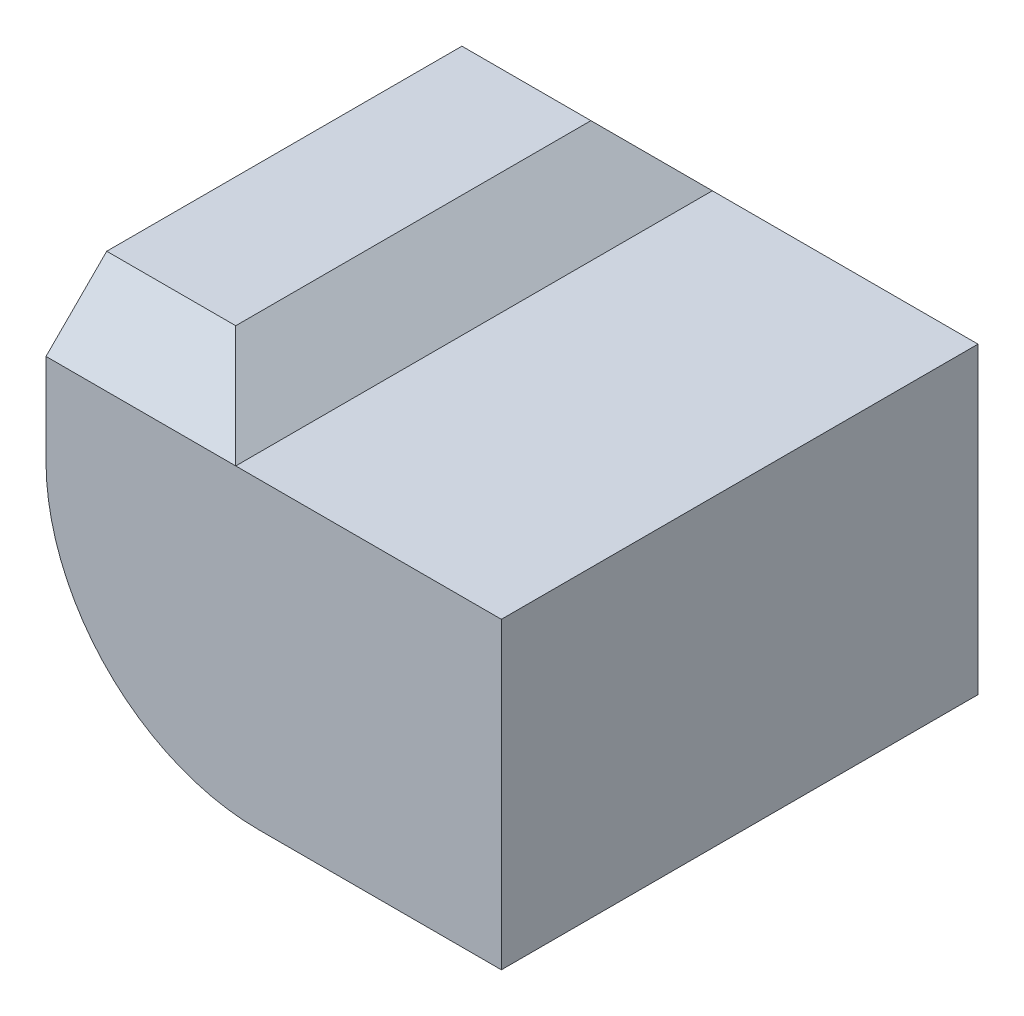
SolidWorks part; units mm, degrees
ref_plane "Front Plane" through (0, 0, 0) normal (0, 0, 1) x (1, 0, 0)
ref_plane "Top Plane" through (0, 0, 0) normal (0, 1, 0) x (1, 0, 0)
ref_plane "Right Plane" through (0, 0, 0) normal (1, 0, 0) x (0, 0, -1)
sketch "Sketch1" plane through (0, 0, 0) normal (0, 0, 1) x (1, 0, 0)
  line L1 (-175, -150) -> (175, -150)
  line L2 (-175, -150) -> (-175, 150)
  line L3 (-175, 150) -> (175, 150)
  line L4 (175, -150) -> (175, 150)
  line L5 (-175, -150) -> (175, 150) construction
  line L6 (-175, 150) -> (175, -150) construction
  point P0 (0, 0)
  dimension "D1" = 350
  dimension "D2" = 300
extrude "Boss-Extrude1" add sketch "Sketch1" along normal blind 117 and the other way blind 117
sketch "Sketch3" plane through (0, 0, 0) normal (0, 0, -1) x (-1, 0, 0)
  line L1 (-175, -150) -> (175, -150)
  line L2 (-175, -150) -> (-175, 150)
  line L3 (-175, 150) -> (175, 150)
  line L4 (175, -150) -> (175, 150)
  line L5 (-175, -150) -> (175, 150) construction
  line L6 (-175, 150) -> (175, -150) construction
  line L7 (175, 150) -> (-75, 150)
  line L8 (175, 150) -> (175, 50)
  line L9 (175, 50) -> (-75, 50)
  line L10 (-75, 150) -> (-75, 50)
  point P0 (0, 0)
  dimension "D2" = 250
  dimension "D3" = 100
extrude "Boss-Extrude2" add sketch "Sketch3" along normal blind 200 and the other way blind 200 contours L1 L2 L3 L10 L9 L4 region at (15.625, -31.25, 0)
sketch "Sketch4" plane through (0, 0, -117) normal (0, 0, -1) x (-1, 0, 0)
  line L0 (175, 150) -> (175, 50) construction
  line L1 (175, 150) -> (-75, 150)
  line L2 (175, 150) -> (175, 90)
  line L3 (175, 90) -> (-75, 90)
  line L4 (-75, 150) -> (-75, 90)
  line L5 (-75, 150) -> (-75, 50) construction
  dimension "D1" = 60
extrude "Cut-Extrude1" cut sketch "Sketch4" against normal blind 540
sketch "Sketch6" plane through (0, 0, -117) normal (0, 0, -1) x (-1, 0, 0)
  line L0 (175, 50) -> (-75, 50) construction
  line L1 (-188.8194, 158.1004) -> (90, 158.1004)
  line L2 (-188.8194, 158.1004) -> (-188.8194, 50)
  line L3 (-188.8194, 50) -> (90, 50)
  line L4 (90, 158.1004) -> (90, 50)
extrude "Cut-Extrude2" cut sketch "Sketch6" against normal blind 540 and the other way blind 138
chamfer "Chamfer1" distance 40 angle 45 1 edges at (-90, 50, 0)
chamfer "Chamfer2" distance 40 angle 45 2 edges at (-112.5, 50, 117) (-112.5, 50, -117)
fillet "Fillet1" radius 140 1 edges at (-175, -150, 0)
sketch "Sketch7" plane through (0, 0, -200) normal (0, 0, -1) x (-1, 0, 0)
  line L0 (-125, 50) -> (-125, -150)
  line L1 (175, 50) -> (-175, 50) construction
  line L2 (-175, -150) -> (35, -150) construction
  line L3 (-125, -150) -> (-196.6342, -174.3761)
  line L4 (-196.6342, -174.3761) -> (-210.8757, 102.3631)
  line L5 (-210.8757, 102.3631) -> (-125, 50)
  line L6 (-175, -150) -> (-175, 50) construction
  dimension "D1" = 50
extrude "Cut-Extrude3" cut sketch "Sketch7" against normal blind 602
sketch "Sketch8" plane through (-175, 0, 0) normal (-1, 0, 0) x (0, 0, 1)
  line L0 (157, 50) -> (157, -180.6533)
  line L1 (157, -180.6533) -> (404.2756, -197.1356)
  line L2 (404.2756, -197.1356) -> (273.0173, 154.6367)
  line L3 (273.0173, 154.6367) -> (157, 50)
  line L4 (-157, 50) -> (-157, -188.8945)
  line L5 (-157, -188.8945) -> (-332.7435, -205.0256)
  line L6 (-332.7435, -205.0256) -> (-278.2888, 167.108)
  line L7 (-278.2888, 167.108) -> (-157, 50)
extrude "Cut-Extrude4" cut sketch "Sketch8" against normal blind 602
